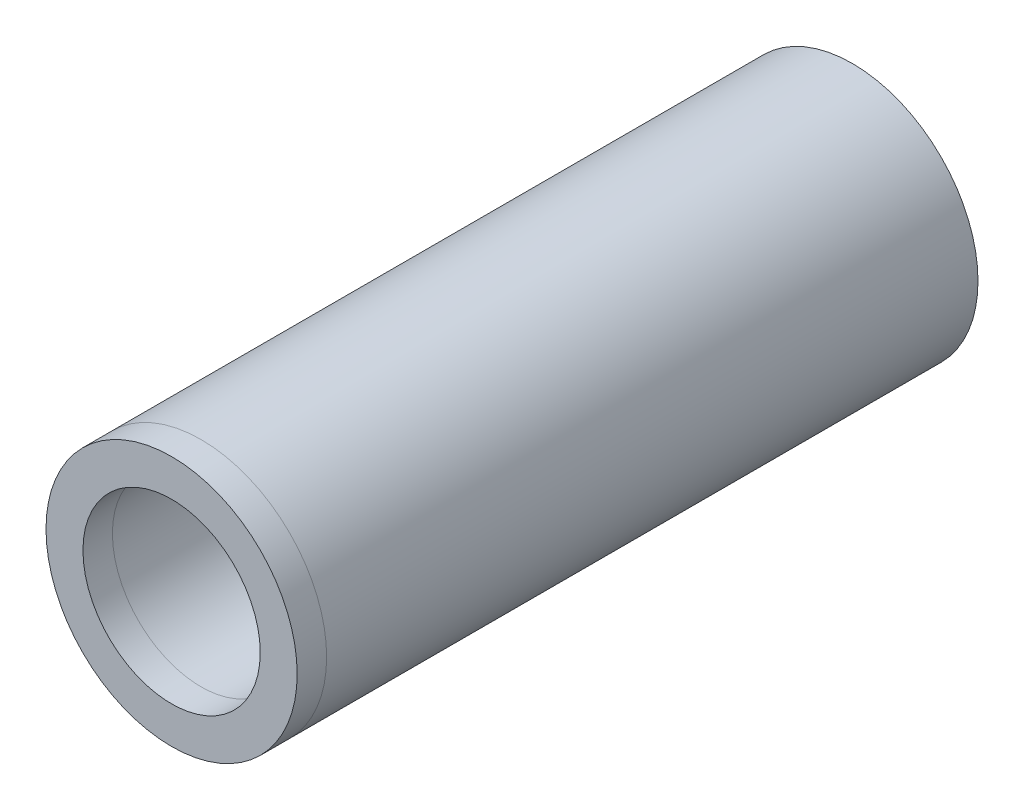
SolidWorks part; units mm, degrees
material "Silicon Rubber"
ref_plane "X-Y Datum" through (0, 0, 0) normal (0, 0, 1) x (1, 0, 0)
ref_plane "X-Z Datum" through (0, 0, 0) normal (0, 1, 0) x (1, 0, 0)
ref_plane "Y-Z Datum" through (0, 0, 0) normal (1, 0, 0) x (0, 0, -1)
sketch3d "3DSketch1"
  line L0 (0, 0, 0) -> (0, 0, 69.9844)
  line L1 (0, 0, -3) -> (0, 0, 24.5) construction
  line L2 (0, 0, 19.6) -> (0, 0, 24.5) construction
  line L3 (0, 0, 69.9844) -> (0, 0, 73.1504)
  circle A6 centre (3.5474, -0.0035, 70.2948) radius 9.525 construction
  point P9 (5.2014, -0.0051, 60.9145)
sweep "Sweep1" add path "3DSketch1" circular profile diameter 26.9875 parameters "D3"=26.9875
sweep "Cut-Sweep1" cut path "3DSketch1<2>" circular profile diameter 19.05 parameters "D3"=19.05
sketch3d "3DSketch1<2>" same geometry as "3DSketch1"
